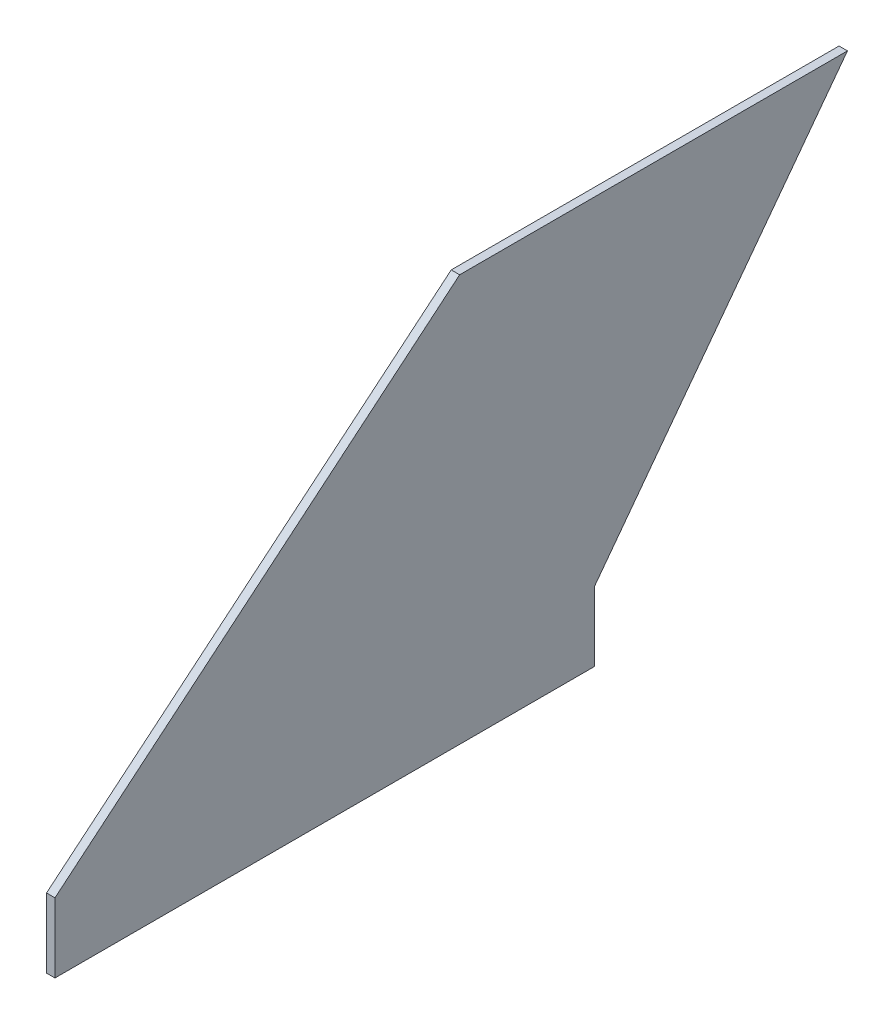
SolidWorks part; units mm, degrees
ref_plane "Front Plane" through (0, 0, 0) normal (0, 0, 1) x (1, 0, 0)
ref_plane "Top Plane" through (0, 0, 0) normal (0, 1, 0) x (1, 0, 0)
ref_plane "Right Plane" through (0, 0, 0) normal (1, 0, 0) x (0, 0, -1)
sketch "Sketch2" plane through (0, 0, 0) normal (1, 0, 0) x (0, 0, -1)
  line L0 (0, 0) -> (152.4, 127)
  line L1 (0, -26.1493) -> (203.2, -26.1493)
  line L2 (0, -26.1493) -> (0, 0)
  line L3 (0, 0) -> (203.2, 0) construction
  line L4 (203.2, -26.1493) -> (203.2, 0)
  line L5 (0, -26.1493) -> (203.2, 0) construction
  line L6 (0, 0) -> (203.2, -26.1493) construction
  line L7 (152.4, 127) -> (298.45, 127)
  line L8 (298.45, 127) -> (203.2, 0)
  point P0 (101.6, -13.0746)
  dimension "D1" = 152.4
  dimension "D2" = 127
  dimension "D3" = 298.45
  dimension "D4" = 203.2
  dimension "D5" = 26.1493
extrude "Boss-Extrude1" add sketch "Sketch2" along normal blind 3.175
equation "\"AIRFRAME_OD\"= 5.15in"
equation "\"AIRFRAME_ID\"= 5.00in"
equation "\"FLAT_T\"= 0.125in"
equation "\"COUPLER_OD\"= 4.998in"
equation "\"COUPLER_ID\"= 4.88in"
equation "\"NOSE_EXP_L\"= 27in"
equation "\"NOSE_SHOULDER_L\"= 5in"
equation "\"MAIN_L\"= 30in"
equation "\"RECO_COUP_L\"= 10in"
equation "\"RECO_SWITCH_L\"= 2in"
equation "\"RECO_ROD_X\"= 3.5in"
equation "\"DROGUE_L\"= 20in"
equation "\"ATS_FORE_COUP_L\"= 5.5in"
equation "\"ATS_AFT_COUP_L\"= 4.5in"
equation "\"ATS_ROD_X\"= 3in"
equation "\"LOWER_L\"= 30in"
equation "\"FIN_ROOT\"= 8in"
equation "\"FIN_X\"= 0.75in"
equation "\"FIN_N\"= 4"
equation "\"MOTOR_OD\"= 3.091in"
equation "\"MOTOR_ID\"= 3.00in"
equation "\"MOTOR_L\"= 14in"
equation "\"CR_AFT_X\"= 0.5in"
equation "\"CR_FORE_X\"= 9.25in"
equation "\"D1@Boss-Extrude1\"=\"FLAT_T\""
equation "\"D4@Sketch2\"=\"FIN_ROOT\""
equation "\"D5@Sketch2\"=(\"AIRFRAME_OD\"-\"MOTOR_OD\")*0.5"
equation "\"MOTOR_LOWER_X\"= 2in"
